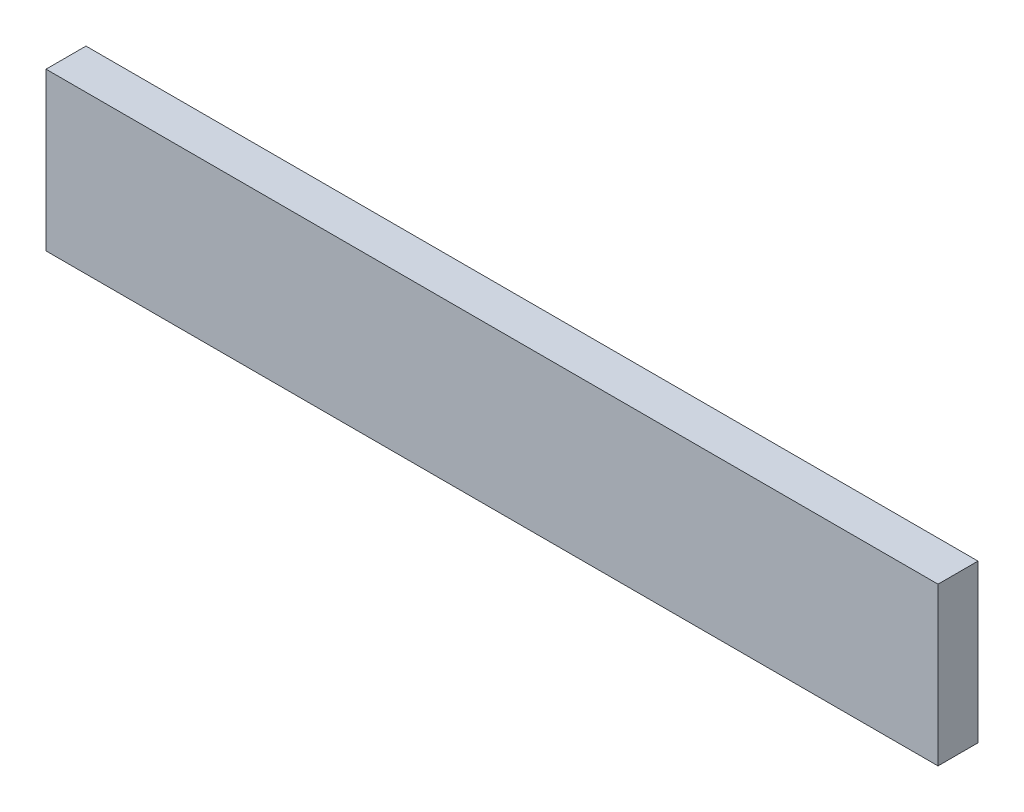
SolidWorks part; units mm, degrees
material "NEOPRENE"
ref_plane "Front Plane" through (0, 0, 0) normal (0, 0, 1) x (1, 0, 0)
ref_plane "Top Plane" through (0, 0, 0) normal (0, 1, 0) x (1, 0, 0)
ref_plane "Right Plane" through (0, 0, 0) normal (1, 0, 0) x (0, 0, -1)
ref_axis "Axis1" through (0, 0, 0) along (0, 1, 0)
sketch "Sketch1" plane through (0, 0, 0) normal (0, 0, 1) x (1, 0, 0)
  line L1 (34, 6) -> (-34, 6)
  line L2 (34, 6) -> (34, -6)
  line L3 (34, -6) -> (-34, -6)
  line L4 (-34, 6) -> (-34, -6)
  line L5 (34, 6) -> (-34, -6) construction
  line L6 (34, -6) -> (-34, 6) construction
  point P0 (0, 0)
  dimension "D1" = 12
  dimension "D2" = 68
extrude "Boss-Extrude1" add sketch "Sketch1" along normal blind 3.048
